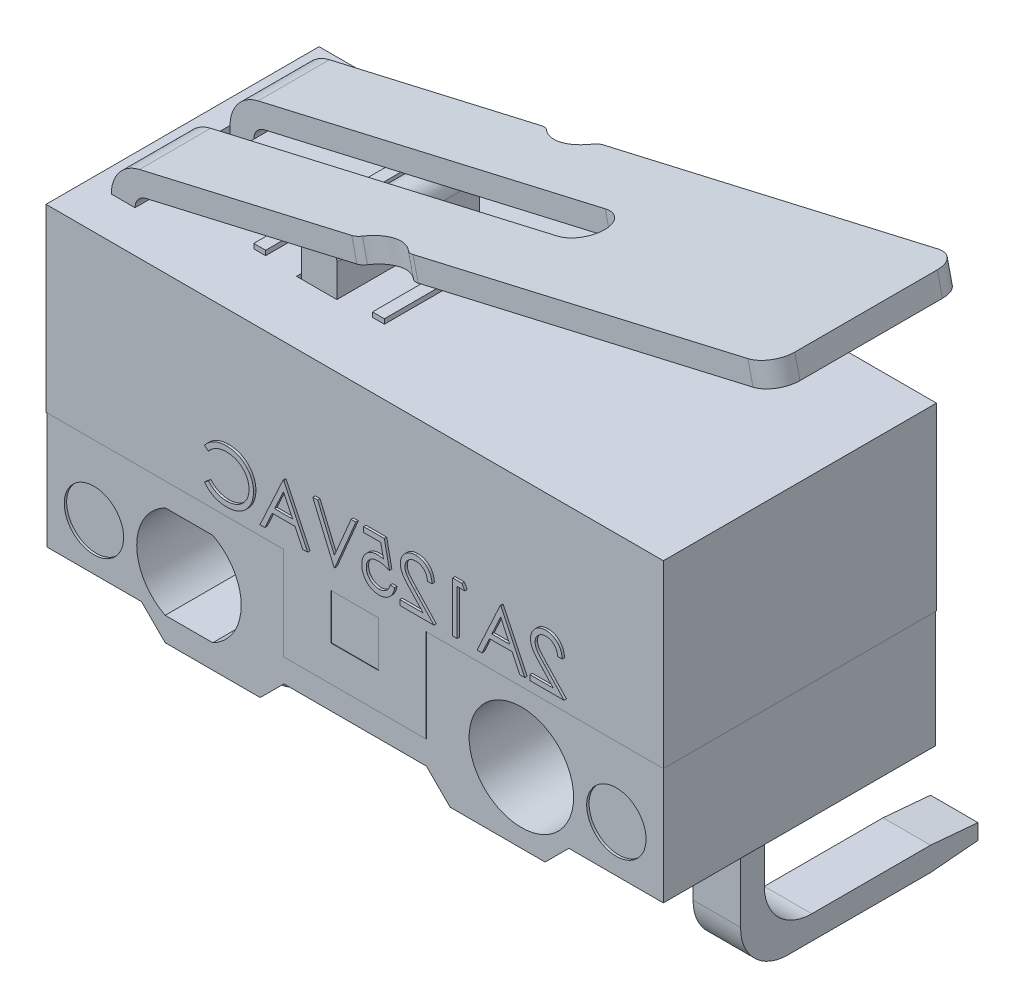
SolidWorks part; units mm, degrees
ref_plane "Plan de face" through (0, 0, 0) normal (0, 0, 1) x (1, 0, 0)
ref_plane "Plan de dessus" through (0, 0, 0) normal (0, 1, 0) x (1, 0, 0)
ref_plane "Plan de droite" through (0, 0, 0) normal (1, 0, 0) x (0, 0, -1)
sketch "Esquisse1" plane through (0, 0, 0) normal (0, 0, 1) x (1, 0, 0)
  line L1 (-6.5, 3.375) -> (6.5, 3.375)
  line L2 (-6.5, 3.375) -> (-6.5, -3.375)
  line L3 (-6.5, -3.375) -> (6.5, -3.375)
  line L4 (6.5, 3.375) -> (6.5, -3.375)
  line L5 (-6.5, 3.375) -> (6.5, -3.375) construction
  line L6 (-6.5, -3.375) -> (6.5, 3.375) construction
  point P0 (0, 0)
  dimension "D1" = 6.75
  dimension "D2" = 13
extrude "Boss.-Extru.1" add sketch "Esquisse1" along normal blind 5.75
ref_plane "Plan1" through (0, 0, 2.875) normal (0, 0, 1) x (1, 0, 0)
sketch "Esquisse6" plane through (0, 0, 5.75) normal (0, 0, 1) x (1, 0, 0)
  line L0 (-6.5, -2.875) -> (-4.5, -2.875)
  line L1 (-6.5, 3.375) -> (-6.5, -3.375) construction
  line L2 (-4.5, -2.875) -> (-4, -3.375)
  line L3 (-6.5, -3.375) -> (6.5, -3.375) construction
  line L4 (-4, -3.375) -> (-2, -3.375)
  line L5 (-2, -3.375) -> (-1.5, -2.875)
  line L6 (-1.5, -2.875) -> (1.5, -2.875)
  line L7 (1.5, -2.875) -> (2, -3.375)
  line L8 (2, -3.375) -> (4, -3.375)
  line L9 (4, -3.375) -> (4.5, -2.875)
  line L10 (4.5, -2.875) -> (6.5, -2.875)
  line L11 (6.5, -3.375) -> (6.5, 3.375) construction
  line L12 (6.5, -2.875) -> (6.5, -4.2145)
  line L13 (6.5, -4.2145) -> (-6.5, -4.2145)
  line L14 (-6.5, -4.2145) -> (-6.5, -2.875)
  dimension "D1" = 0.5
  dimension "D2" = 135
  dimension "D3" = 135
  dimension "D4" = 135
  dimension "D5" = 2
  dimension "D6" = 2
  dimension "D7" = 2
  dimension "D8" = 2
extrude "Enlèv. mat.-Extru.1" cut sketch "Esquisse6" against normal up to surface (5.75 mm away) up to face at (0, 0, 0)
sketch "Esquisse4" plane through (0, 0, 2.875) normal (0, 0, 1) x (1, 0, 0)
  line L0 (-5.5, -2.875) -> (-5.5, -6.125)
  line L9 (-4.5, -6.125) -> (-4.5, -2.875)
  line L10 (-4.5, -2.875) -> (-5.5, -2.875)
  line L11 (-5, -2.875) -> (-5, -7.9439) construction
  line L15 (-5.5, -6.125) -> (-4.5, -6.125)
  line L16 (-4.5, -2.875) -> (-6.5, -2.875) construction
  line L17 (-6.5, 3.375) -> (-6.5, -2.875) construction
  dimension "D1" = 1.5
  dimension "D2" = 1
  dimension "D4" = 3.25
extrude "Boss.-Extru.2" add sketch "Esquisse4" along normal blind 0.25 and the other way blind 0.25
sketch "Esboço2" plane through (-5.5, 0, 0) normal (-1, 0, 0) x (0, 0, 1)
  line L1 (2.625, -6.125) -> (7.625, -6.125)
  line L2 (2.625, -6.125) -> (2.625, -5.625)
  line L3 (2.625, -5.625) -> (7.625, -5.625)
  line L4 (7.625, -6.125) -> (7.625, -5.625)
  dimension "D1" = 5
  dimension "D2" = 0.5
extrude "Ressalto-extrusão1" add sketch "Esboço2" against normal up to surface (1 mm away) up to face at (-4.5, -4.5, 2.875)
fillet "Filete1" radius 1 2 edges at (-5, -6.125, 2.625) (-5, -5.625, 3.125)
sketch "Esquisse7" plane through (0, 0, 5.75) normal (0, 0, 1) x (1, 0, 0)
  line L0 (-4, -2.875) -> (-3, -2.875)
  line L1 (-4, -0.9154) -> (-3, -0.9154)
  line L2 (-3.5, -1.8952) -> (3.5, -1.8952) construction
  line L3 (-4, -3.375) -> (-2, -3.375) construction
  line L4 (-6.5, 3.375) -> (-6.5, -2.875) construction
  line L5 (6.5, -2.875) -> (6.5, 3.375) construction
  arc A0 (-4, -0.9154) -> (-4, -2.875) centre (-3.5, -1.8952) ccw
  arc A1 (-3, -0.9154) -> (-3, -2.875) centre (-3.5, -1.8952) cw
  circle A2 centre (3.5, -1.8952) radius 1.1
  dimension "D1" = 1.1
  dimension "D3" = 1.1
  dimension "D4" = 2.2
  dimension "D2" = 1
  dimension "D5" = 0.5
  dimension "D6" = 3
  dimension "D7" = 3
extrude "Enlèv. mat.-Extru.2" cut sketch "Esquisse7" against normal up to surface (5.75 mm away) up to face at (0, -2, 0)
sketch "Esquisse8" plane through (0, 0, 5.75) normal (0, 0, 1) x (1, 0, 0)
  line L0 (-6.5, -0.4154) -> (-1.5, -0.4154)
  line L1 (-6.5, 3.375) -> (-6.5, -2.875) construction
  line L2 (-1.5, -0.4154) -> (-1.5, -2.375)
  line L3 (-1.5, -2.375) -> (1.5, -2.375)
  line L4 (1.5, -2.375) -> (1.5, -0.4154)
  line L5 (1.5, -0.4154) -> (6.5, -0.4154)
  line L6 (6.5, -2.875) -> (6.5, 3.375) construction
  line L7 (6.5, -0.4154) -> (6.5, -4.9919)
  line L8 (6.5, -4.9919) -> (-6.5, -4.9919)
  line L9 (-6.5, -4.9919) -> (-6.5, -0.4154)
  line L10 (1.5, -2.875) -> (-1.5, -2.875) construction
  line L11 (-3, -0.9154) -> (-4, -0.9154) construction
  line L13 (-0.5, -0.6654) -> (0.5, -0.6654)
  line L14 (-0.5, -0.6654) -> (-0.5, -1.625)
  line L15 (-0.5, -1.625) -> (0.5, -1.625)
  line L16 (0.5, -0.6654) -> (0.5, -1.625)
  line L17 (-0.5, -0.6654) -> (0.5, -1.625) construction
  line L18 (-0.5, -1.625) -> (0.5, -0.6654) construction
  point P21 (0, -1.1452)
  dimension "D1" = 0.5
  dimension "D2" = 0.5
  dimension "D3" = 0.25
  dimension "D4" = 1
  dimension "D5" = 1
  dimension "D6" = 0.75
extrude "Enlèv. mat.-Extru.3" cut sketch "Esquisse8" against normal blind 0.01
sketch "Esquisse9" plane through (0, 0, 5.74) normal (0, 0, 1) x (1, 0, 0)
  line L0 (-5.5, -1.8952) -> (5.5, -1.8952) construction
  line L1 (6.5, -2.875) -> (6.5, -0.4154) construction
  line L2 (-6.5, -0.4154) -> (-6.5, -2.875) construction
  circle A0 centre (-5.5, -1.8952) radius 0.625
  circle A1 centre (5.5, -1.8952) radius 0.625
  point P4 (3.5, -1.8952)
  dimension "D1" = 1.25
  dimension "D2" = 1.25
  dimension "D3" = 1
  dimension "D4" = 1
extrude "Enlèv. mat.-Extru.4" cut sketch "Esquisse9" against normal blind 0.05
mirror "Symétrie1" about plane through (0, 0, 2.875) normal (0, 0, 1) of "Enlèv. mat.-Extru.4", "Enlèv. mat.-Extru.3"
sketch "Esquisse10" plane through (-6.5, 0, 0) normal (-1, 0, 0) x (0, 0, 1)
  line L1 (0.01, -2.875) -> (5.74, -2.875)
  line L2 (0.01, -2.875) -> (0.01, -0.4154)
  line L3 (0.01, -0.4154) -> (5.74, -0.4154)
  line L4 (5.74, -2.875) -> (5.74, -0.4154)
extrude "Enlèv. mat.-Extru.5" cut sketch "Esquisse10" against normal blind 0.01
sketch "Esquisse11" plane through (6.5, 0, 0) normal (1, 0, 0) x (0, 0, -1)
  line L1 (-5.74, -2.875) -> (-0.01, -2.875)
  line L2 (-5.74, -2.875) -> (-5.74, -0.4154)
  line L3 (-5.74, -0.4154) -> (-0.01, -0.4154)
  line L4 (-0.01, -2.875) -> (-0.01, -0.4154)
extrude "Enlèv. mat.-Extru.6" cut sketch "Esquisse11" against normal blind 0.01
sketch "Esquisse12" plane through (0, 0, 5.75) normal (0, 0, 1) x (1, 0, 0)
  line L0 (-6.2, 0.5846) -> (-4.55, 0.5846) construction
  line L4 (-1, 0.5846) -> (2.5, 0.5846) construction
  line L5 (3.5, 0.5846) -> (6.2, 0.5846) construction
  line L6 (-1.5, -0.4154) -> (-6.5, -0.4154) construction
  line L7 (-6.5, 3.375) -> (-6.5, -0.4154) construction
  line L8 (6.5, -0.4154) -> (6.5, 3.375) construction
  text T0 "C" font "Century Gothic" height in points 5
  text T1 "NO" font "Century Gothic" height in points 5
  text T2 "NC" font "Century Gothic" height in points 5
  dimension "D1" = 1
  dimension "D2" = 1.65
  dimension "D3" = 0.3
  dimension "D4" = 0.3
  dimension "D5" = 2.7
  dimension "D6" = 3.5
  dimension "D7" = 1
extrude "Boss.-Extru.3" add sketch "Esquisse12" along normal blind 0.01
sketch "Esquisse13" plane through (0, 0, 2.875) normal (0, 0, 1) x (1, 0, 0)
  line L0 (-1.75, 4) -> (-1.75, 3.375)
  line L1 (6.5, 3.375) -> (-6.5, 3.375) construction
  line L2 (-1.75, 3.375) -> (-2.5, 3.375)
  line L3 (-2.5, 3.375) -> (-2.5, 4)
  line L4 (-4.7467, 4.375) -> (-2.1308, 4.375) construction
  line L5 (-6.5, 3.375) -> (-6.5, -0.4154) construction
  line L6 (-3.5, 3.375) -> (-3.5, 3.475)
  line L7 (-3.5, 3.475) -> (-3.25, 3.475)
  line L8 (-3.25, 3.475) -> (-3.25, 3.375)
  line L9 (-3.25, 3.375) -> (-3.5, 3.375)
  line L10 (-1, 3.375) -> (-1, 3.475)
  line L11 (-1, 3.475) -> (-0.75, 3.475)
  line L12 (-0.75, 3.475) -> (-0.75, 3.375)
  line L13 (-0.75, 3.375) -> (-1, 3.375)
  arc A0 (-2.5, 4) -> (-1.75, 4) centre (-2.125, 4) cw
  dimension "D1" = 0.75
  dimension "D2" = 1
  dimension "D3" = 4
  dimension "D4" = 0.1
  dimension "D5" = 0.75
  dimension "D6" = 0.75
  dimension "D7" = 0.25
  dimension "D8" = 0.25
extrude "Boss.-Extru.4" add sketch "Esquisse13" along normal blind 1.5 and the other way blind 1.5
sketch "Esquisse14" plane through (0, 3.375, 0) normal (0, 1, 0) x (1, 0, 0)
  line L1 (-2.5, -1.375) -> (-1.75, -1.375)
  line L2 (-2.5, -1.375) -> (-2.5, -4.375)
  line L3 (-2.5, -4.375) -> (-1.75, -4.375)
  line L4 (-1.75, -1.375) -> (-1.75, -4.375)
  line L8 (-6.5, -5.75) -> (-6.5, 0) construction
  line L9 (-6, -0.875) -> (-5.5, -0.875)
  line L10 (-6, -0.875) -> (-6, -4.875)
  line L11 (-6, -4.875) -> (-5.5, -4.875)
  line L12 (-2.55, -1.325) -> (-2.55, -4.425)
  line L13 (-2.55, -4.425) -> (-1.7, -4.425)
  line L14 (-1.7, -4.425) -> (-1.7, -1.325)
  line L15 (-1.7, -1.325) -> (-2.55, -1.325)
  line L16 (-2.55, -1.325) -> (-2.55, -4.425)
  line L17 (-2.55, -4.425) -> (-1.7, -4.425)
  line L18 (-1.7, -4.425) -> (-1.7, -1.325)
  line L19 (-1.7, -1.325) -> (-2.55, -1.325)
  line L20 (-5.5, -0.875) -> (-5.5, -4.875)
  line L21 (-6, -2.875) -> (-3.9155, -2.875) construction
  line L22 (-3.1625, -2.875) -> (3.1625, -2.875) construction
  dimension "D2" = 0.5
  dimension "D3" = 0.5
  dimension "D4" = 4
  dimension "D1" = 0.05
extrude "Enlèv. mat.-Extru.7" cut sketch "Esquisse14" against normal blind 2
sketch "Esquisse16" plane through (0, 0, 0.875) normal (0, 0, 1) x (1, 0, 0)
  line L0 (-6, 2.375) -> (-5.5, 2.375)
  line L1 (-5.5, 2.375) -> (-5.5, 3.375)
  line L2 (-5.2748, 3.6581) -> (8, 6.7211)
  line L3 (8, 6.7211) -> (7.8921, 7.1888)
  line L4 (7.8921, 7.1888) -> (-5.4072, 4.1201)
  line L5 (-6, 3.375) -> (-6, 2.375)
  line L6 (-6.5, 3.375) -> (-6.5, -0.4154) construction
  line L7 (6.5, 3.375) -> (-6.5, 3.375) construction
  line L8 (8, 6.7211) -> (8, 3.9001) construction
  line L9 (6.5, -0.4154) -> (6.5, 3.375) construction
  line L10 (6.5, 2.5145) -> (6.5, 9.8405) construction
  arc A0 (-5.5, 3.375) -> (-5.2748, 3.6581) centre (-5.2095, 3.375) cw
  arc A2 (-1.75, 4) -> (-2.5, 4) centre (-2.125, 4) ccw construction
  arc A3 (-6, 3.375) -> (-5.4072, 4.1201) centre (-5.2353, 3.375) cw
  point P8 (6.5, 6.375)
  dimension "D1" = 0.5
  dimension "D2" = 0.5
  dimension "D3" = 0.48
  dimension "D4" = 1
  dimension "D5" = 1.5
  dimension "D6" = 3
extrude "Boss.-Extru.13" add sketch "Esquisse16" along normal up to surface (4 mm away) separate body contours A3 L4 L3 L2 A0 L1 L0 L5 up to face at (-5.75, 2.375, 4.875)
sketch "Esquisse17" plane through (0, 0, 2.875) normal (0, 0, 1) x (1, 0, 0)
  line L6 (-5.4072, 4.1201) -> (2.3879, 5.9188)
  line L7 (7.8921, 7.1888) -> (-5.4072, 4.1201) construction
  line L8 (2.3879, 5.9188) -> (2.4959, 5.4511)
  line L9 (-5.2748, 3.6581) -> (8, 6.7211) construction
  line L10 (2.4959, 5.4511) -> (-5.2748, 3.6581)
  line L12 (-6, 3.375) -> (-6, 2.375)
  line L13 (-6, 2.375) -> (-5.5, 2.375)
  line L14 (-5.5, 2.375) -> (-5.5, 3.375)
  line L15 (-5.2748, 3.6581) -> (8, 6.7211)
  line L16 (8, 6.7211) -> (7.8921, 7.1888)
  line L17 (7.8921, 7.1888) -> (-5.4072, 4.1201)
  line L18 (-6, 3.375) -> (-6, 2.375)
  line L19 (-6, 2.375) -> (-5.5, 2.375)
  line L20 (-5.5, 2.375) -> (-5.5, 3.375)
  arc A4 (-5.4072, 4.1201) -> (-6, 3.375) centre (-5.2353, 3.375) ccw
  arc A5 (-5.2748, 3.6581) -> (-5.5, 3.375) centre (-5.2095, 3.375) ccw
  arc A6 (-5.4072, 4.1201) -> (-6, 3.375) centre (-5.2353, 3.375) ccw
  arc A7 (-5.2748, 3.6581) -> (-5.5, 3.375) centre (-5.2095, 3.375) ccw
  dimension "D2" = 8
  dimension "D1" = 0
extrude "Enlèv. mat.-Extru.8" cut sketch "Esquisse17" against normal blind 0.5 and the other way blind 0.5
fillet "Congé1" radius 0.5 2 edges at (2.4419, 5.6849, 3.375) (2.4419, 5.6849, 2.375)
sketch "Esquisse18" plane through (-1.176, 5.0964, 0) normal (-0.2248, 0.9744, 0) x (0.9744, 0.2248, 0)
  line L0 (3.6575, -1.5522) -> (3.6575, -4.3731) construction
  line L1 (1.6575, 0.7356) -> (1.6575, -6.4529) construction
  line L3 (1.6575, -4.625) -> (-0.9803, -4.625) construction
  line L4 (9.3063, -4.875) -> (-4.3425, -4.875) construction
  line L5 (1.6575, -1.125) -> (-0.2394, -1.125) construction
  line L6 (9.3063, -0.875) -> (-4.3425, -0.875) construction
  arc A0 (3.6575, -2.875) -> (3.1575, -2.375) centre (3.1575, -2.875) ccw construction
  circle A1 centre (0.9075, -5.375) radius 0.75
  circle A2 centre (0.9075, -0.375) radius 0.75
  dimension "D2" = 1.5
  dimension "D3" = 1.5
  dimension "D1" = 2
  dimension "D4" = 0.25
  dimension "D5" = 0.25
extrude "Enlèv. mat.-Extru.9" cut sketch "Esquisse18" against normal blind 0.5
fillet "Congé2" radius 0.25 4 edges at (-0.7824, 4.941, 0.875) (0.307, 5.1923, 0.875) (0.307, 5.1923, 4.875) (-0.7824, 4.941, 4.875)
fillet "Congé3" radius 0.5 2 edges at (7.946, 6.955, 0.875) (7.946, 6.955, 4.875)
sketch "Esquisse19" plane through (0, 0, 0) normal (0, 0, -1) x (-1, 0, 0)
  line L0 (-4.5, -0.1654) -> (5.7239, -0.1654) construction
  line L1 (-6.5, -0.4154) -> (-1.5, -0.4154) construction
  line L2 (-6.5, -0.4154) -> (-6.5, 3.375) construction
  text T0 "2A125VAC" font "Century Gothic" height in points 4
  dimension "D1" = 0.25
  dimension "D2" = 2
extrude "Boss.-Extru.14" add sketch "Esquisse19" along normal blind 0.05
pattern_linear "Padrão linear2" count 3 spacing 5 along (1, 0, 0) of "Boss.-Extru.2", "Ressalto-extrusão1", "Filete1"
chamfer "Chanfro1" distance 1 angle 5 3 edges at (-5, -5.625, 7.625) (0, -5.625, 7.625) (5, -5.625, 7.625)
chamfer "Chanfro2" distance 1 angle 5 3 edges at (-5, -6.125, 7.625) (0, -6.125, 7.625) (5, -6.125, 7.625)
ref_plane "Plano1" through (0, 0, -10) normal (0, 0, 1) x (1, 0, 0)
mirror "Espelhar5" about plane through (0, 0, -10) normal (0, 0, 1) of bodies 119 116
delete or keep bodies "Corpo-Excluir/Manter 1" type delete bodies bodies 119
delete or keep bodies "Corpo-Excluir/Manter 2" type delete bodies bodies 116
